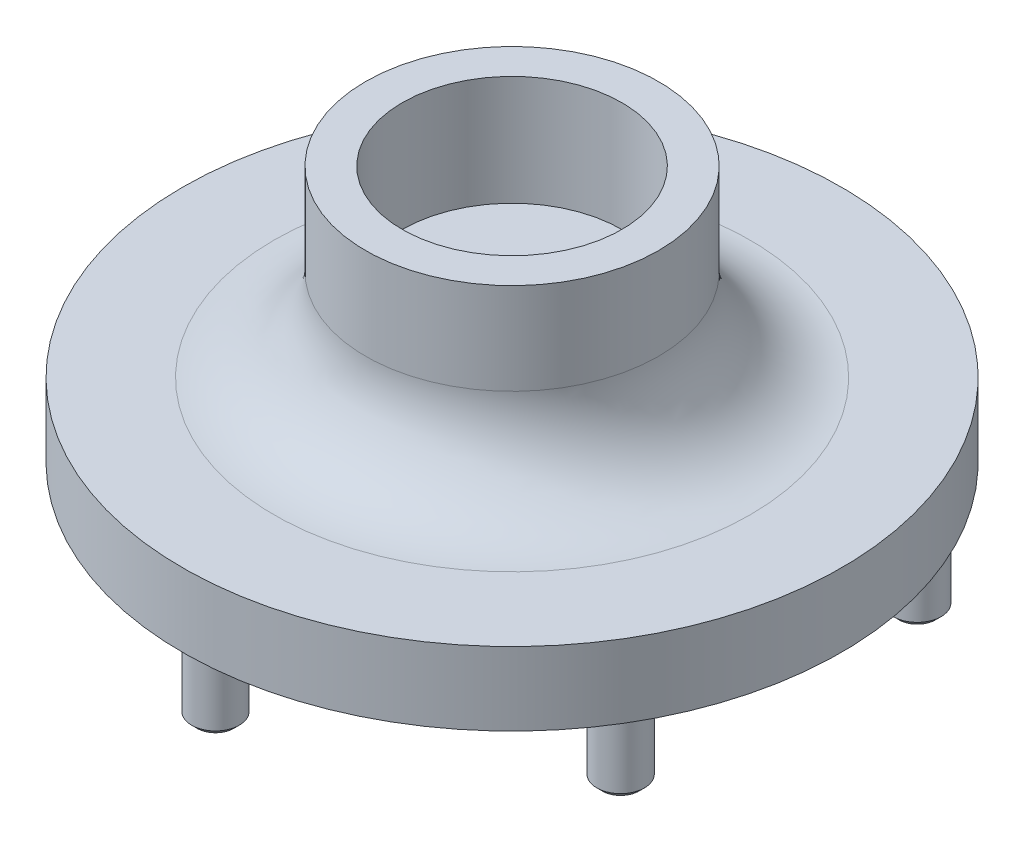
SolidWorks part; units mm, degrees
ref_plane "Front Plane" through (0, 0, 0) normal (0, 0, 1) x (1, 0, 0)
ref_plane "Top Plane" through (0, 0, 0) normal (0, 1, 0) x (1, 0, 0)
ref_plane "Right Plane" through (0, 0, 0) normal (1, 0, 0) x (0, 0, -1)
sketch "Sketch1" plane through (0, 0, 0) normal (0, 0, 1) x (1, 0, 0)
  line L0 (0, 0) -> (-30, 0)
  line L1 (-30, 0) -> (-30, 30)
  line L2 (-30, 30) -> (-50, 30)
  line L3 (-50, 30) -> (-50, 35)
  line L4 (-50, 35) -> (-90, 35)
  line L5 (-90, 35) -> (-90, 55)
  line L6 (-90, 55) -> (-40, 55)
  line L7 (-40, 55) -> (-40, 105)
  line L8 (-40, 105) -> (-30, 105)
  line L9 (-30, 105) -> (-30, 75)
  line L10 (-30, 75) -> (0, 75)
  line L11 (0, 75) -> (0, 0)
  dimension "D1" = 30
  dimension "D2" = 30
  dimension "D3" = 20
  dimension "D4" = 40
  dimension "D5" = 50
  dimension "D6" = 50
  dimension "D7" = 10
  dimension "D8" = 30
  dimension "D9" = 75
  dimension "D10" = 30
revolve "Revolve1" add sketch "Sketch1" angle 360 about L11 region at (-31.4198, 44.8457, 0)
sketch "Sketch2" plane through (0, 55, 0) normal (0, 1, 0) x (1, 0, 0)
  circle A0 centre (0, 81) radius 6.5
  dimension "D1" = 13
  dimension "D2" = 81
extrude "Boss-Extrude2" add sketch "Sketch2" against normal blind 40
pattern_circular "CirPattern15" count 6 over 360 about axis through (0, 75, 0) along (0, 1, 0) of "Boss-Extrude2" reverse direction yes
chamfer "Chamfer1" distance 1.5 angle 45 6 edges at (-66.8981, 15, 46.1292) (6.5, 15, 81) (73.3981, 15, 34.8708) (66.8981, 15, -46.1292) (-6.5, 15, -81) (-73.3981, 15, -34.8708)
fillet "Fillet1" radius 25 2 edges at (-30, 30, 0) (-40, 55, 0)
fillet "Fillet2" radius 15 1 edges at (-30, 0, 0)
